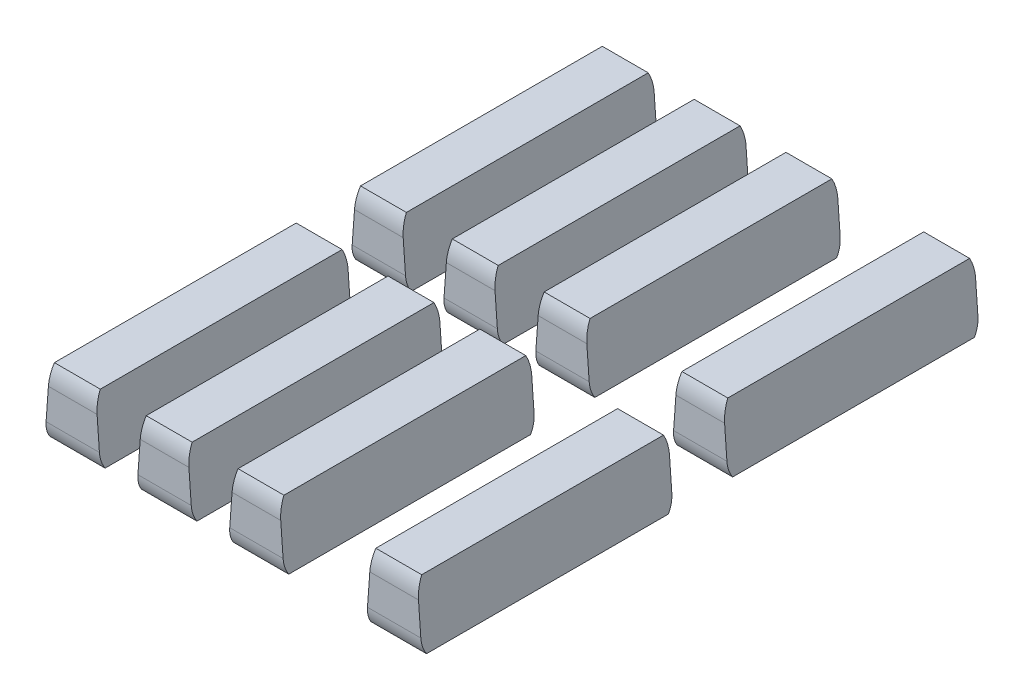
SolidWorks part; units mm, degrees
ref_plane "Front Plane" through (0, 0, 0) normal (0, 0, 1) x (1, 0, 0)
ref_plane "Top Plane" through (0, 0, 0) normal (0, 1, 0) x (1, 0, 0)
ref_plane "Right Plane" through (0, 0, 0) normal (1, 0, 0) x (0, 0, -1)
sketch "Sketch1" plane through (0, 0, 0) normal (0, 1, 0) x (1, 0, 0)
  line L0 (9.1562, 0.75) -> (9.1562, 20.75) construction
  line L1 (-10, 20.75) -> (28.3124, 20.75)
  line L2 (-10, 20.75) -> (-10, -19.25)
  line L3 (-10, -19.25) -> (28.3124, -19.25)
  line L4 (28.3124, 20.75) -> (28.3124, -19.25)
  line L5 (9.1562, 0.75) -> (28.3124, 0.75) construction
  line L6 (-10, 20.75) -> (28.3124, 20.75) construction
sketch "Sketch2" plane through (0, 0, 0) normal (0, 0, 1) x (1, 0, 0)
  line L24 (1.6562, -2.344) -> (1.8141, -4.5) construction
  line L25 (0.1562, -2.344) -> (1.6562, -2.344) construction
  line L26 (-0.0017, -4.5) -> (0.1562, -2.344) construction
  line L27 (1.8141, -4.5) -> (-0.0017, -4.5) construction
  line L28 (3.1562, -2.344) -> (2.9983, -4.5) construction
  line L29 (4.6562, -2.344) -> (3.1562, -2.344) construction
  line L30 (4.8141, -4.5) -> (4.6562, -2.344) construction
  line L31 (2.9983, -4.5) -> (4.8141, -4.5) construction
  line L32 (5.9983, -4.5) -> (6.1562, -2.344) construction
  line L33 (6.1562, -2.344) -> (7.6562, -2.344) construction
  line L34 (7.6562, -2.344) -> (7.8141, -4.5) construction
  line L35 (7.8141, -4.5) -> (5.9983, -4.5) construction
  line L36 (10.6562, -2.344) -> (9.1562, -2.344) construction
  line L37 (9.1562, -2.344) -> (8.9983, -4.5) construction
  line L38 (8.9983, -4.5) -> (10.8141, -4.5) construction
  line L39 (10.8141, -4.5) -> (10.6562, -2.344) construction
  line L40 (12.1562, -2.344) -> (13.6562, -2.344) construction
  line L41 (13.6562, -2.344) -> (13.8141, -4.5) construction
  line L42 (13.8141, -4.5) -> (11.9983, -4.5) construction
  line L43 (11.9983, -4.5) -> (12.1562, -2.344) construction
  line L44 (18.1562, -2.344) -> (16.6562, -2.344) construction
  line L45 (16.6562, -2.344) -> (16.4983, -4.5) construction
  line L46 (16.4983, -4.5) -> (18.3141, -4.5) construction
  line L47 (18.3141, -4.5) -> (18.1562, -2.344) construction
  line L48 (1.6562, -2.344) -> (1.8141, -4.5) construction
  line L49 (0.1562, -2.344) -> (1.6562, -2.344) construction
  line L50 (-0.0017, -4.5) -> (0.1562, -2.344) construction
  line L51 (1.8141, -4.5) -> (-0.0017, -4.5) construction
  line L52 (3.1562, -2.344) -> (2.9983, -4.5) construction
  line L53 (4.6562, -2.344) -> (3.1562, -2.344) construction
  line L54 (4.8141, -4.5) -> (4.6562, -2.344) construction
  line L55 (2.9983, -4.5) -> (4.8141, -4.5) construction
  line L56 (5.9983, -4.5) -> (6.1562, -2.344)
  line L57 (6.1562, -2.344) -> (7.6562, -2.344)
  line L58 (7.6562, -2.344) -> (7.8141, -4.5)
  line L59 (7.8141, -4.5) -> (5.9983, -4.5)
  line L60 (10.6562, -2.344) -> (9.1562, -2.344)
  line L61 (9.1562, -2.344) -> (8.9983, -4.5)
  line L62 (8.9983, -4.5) -> (10.8141, -4.5)
  line L63 (10.8141, -4.5) -> (10.6562, -2.344)
  line L64 (12.1562, -2.344) -> (13.6562, -2.344)
  line L65 (13.6562, -2.344) -> (13.8141, -4.5)
  line L66 (13.8141, -4.5) -> (11.9983, -4.5)
  line L67 (11.9983, -4.5) -> (12.1562, -2.344)
  line L68 (18.1562, -2.344) -> (16.6562, -2.344)
  line L69 (16.6562, -2.344) -> (16.4983, -4.5)
  line L70 (16.4983, -4.5) -> (18.3141, -4.5)
  line L71 (18.3141, -4.5) -> (18.1562, -2.344)
sketch "Sketch3" plane through (0, 0, 0) normal (1, 0, 0) x (0, 0, -1)
  line L0 (-8.95, -4.5) -> (-11.05, -4.5)
  line L1 (-1.05, -4.5) -> (1.05, -4.5)
  line L2 (8.95, -4.5) -> (11.05, -4.5)
  line L4 (-0.9, -4) -> (-0.9, -2.9607) construction
  line L5 (0.9, -4) -> (0.9, -2.9607) construction
  line L6 (9.1, -4) -> (9.1, -2.9607) construction
  line L7 (-9.1, -4) -> (-9.1, -2.9607) construction
  line L8 (-0.9, -4) -> (-0.9, -2.9607)
  line L9 (0.9, -4) -> (0.9, -2.9607)
  line L10 (9.1, -4) -> (9.1, -2.9607)
  line L11 (-9.1, -4) -> (-9.1, -2.9607)
  line L12 (-11.05, -2.344) -> (-11.05, -4.5)
  line L13 (11.05, -2.344) -> (11.05, -4.5)
  line L14 (-1.05, -2.344) -> (1.05, -2.344)
  line L16 (8.95, -2.344) -> (11.05, -2.344)
  line L18 (-8.95, -2.344) -> (-11.05, -2.344)
  arc A5 (0.9, -4) -> (1.05, -4.5) centre (1.8083, -4) ccw construction
  arc A7 (-0.9, -2.9607) -> (-1.05, -2.344) centre (-2.2428, -2.9607) ccw construction
  arc A8 (1.05, -2.344) -> (0.9, -2.9607) centre (2.2428, -2.9607) ccw construction
  arc A9 (9.1, -2.9607) -> (8.95, -2.344) centre (7.7572, -2.9607) ccw construction
  arc A10 (-1.05, -4.5) -> (-0.9, -4) centre (-1.8083, -4) ccw construction
  arc A11 (0.9, -4) -> (1.05, -4.5) centre (1.8083, -4) ccw
  arc A13 (8.95, -4.5) -> (9.1, -4) centre (8.1917, -4) ccw construction
  arc A15 (-9.1, -4) -> (-8.95, -4.5) centre (-8.1917, -4) ccw construction
  arc A16 (-1.05, -4.5) -> (-0.9, -4) centre (-1.8083, -4) ccw
  arc A17 (-9.1, -4) -> (-8.95, -4.5) centre (-8.1917, -4) ccw
  arc A18 (8.95, -4.5) -> (9.1, -4) centre (8.1917, -4) ccw
  arc A19 (-8.95, -2.344) -> (-9.1, -2.9607) centre (-7.7572, -2.9607) ccw construction
  arc A20 (-0.9, -2.9607) -> (-1.05, -2.344) centre (-2.2428, -2.9607) ccw
  arc A21 (1.05, -2.344) -> (0.9, -2.9607) centre (2.2428, -2.9607) ccw
  arc A22 (9.1, -2.9607) -> (8.95, -2.344) centre (7.7572, -2.9607) ccw
  arc A23 (-8.95, -2.344) -> (-9.1, -2.9607) centre (-7.7572, -2.9607) ccw
extrude "Boss-Extrude1" add sketch "Sketch2" along normal up to vertex (11.05 mm away) from vertex up to point (0, -4.5, 11.05) starting at point (0, -4.5, -11.05)
extrude "Cut-Extrude5" cut sketch "Sketch3" along normal through all from vertex starting at point (-0.0017, -4.5, 0)
